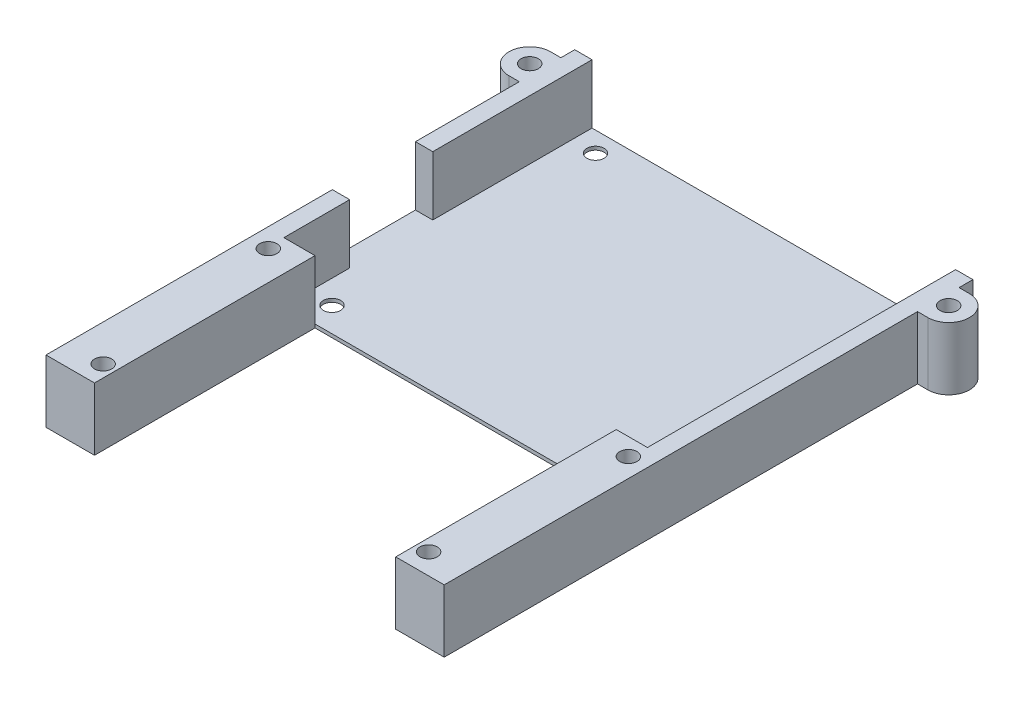
SolidWorks part; units mm, degrees
ref_plane "Front Plane" through (0, 0, 0) normal (0, 0, 1) x (1, 0, 0)
ref_plane "Top Plane" through (0, 0, 0) normal (0, 1, 0) x (1, 0, 0)
ref_plane "Right Plane" through (0, 0, 0) normal (1, 0, 0) x (0, 0, -1)
sketch "Sketch1" plane through (0, 0, 0) normal (0, 1, 0) x (1, 0, 0)
  line L0 (0, 0) -> (0, 76.35) construction
  line L1 (-28.75, 76.35) -> (28.75, 76.35)
  line L2 (28.75, 76.35) -> (28.75, 0)
  line L3 (28.75, 0) -> (21.75, 0)
  line L4 (21.75, 0) -> (21.75, 31.85)
  line L5 (21.75, 31.85) -> (-21.75, 31.85)
  line L6 (-21.75, 31.85) -> (-21.75, 0)
  line L7 (-21.75, 0) -> (-28.75, 0)
  line L8 (-28.75, 0) -> (-28.75, 76.35)
  line L9 (-26.25, 76.35) -> (-26.25, 31.85)
  line L14 (-26.25, 31.85) -> (-21.75, 31.85)
  line L15 (26.25, 76.35) -> (26.25, 31.85)
  line L16 (26.25, 31.85) -> (21.75, 31.85)
  line L17 (28.75, 74.35) -> (30.25, 74.35)
  line L18 (-28.75, 41.35) -> (-26.25, 41.35)
  line L19 (-28.75, 41.35) -> (-28.75, 53.35)
  line L20 (-28.75, 53.35) -> (-26.25, 53.35)
  line L21 (-26.25, 41.35) -> (-26.25, 53.35)
  line L22 (30.25, 68.35) -> (28.75, 68.35)
  line L23 (-30.25, 68.35) -> (-28.75, 68.35)
  line L24 (-28.75, 74.35) -> (-30.25, 74.35)
  arc A0 (30.25, 68.35) -> (30.25, 74.35) centre (30.25, 71.35) ccw
  arc A1 (-30.25, 68.35) -> (-30.25, 74.35) centre (-30.25, 71.35) cw
  point P10 (0, 76.35)
  point P16 (-27.5, 41.35)
  point P17 (-22.85, 73.45)
  point P18 (22.85, 73.45)
  point P23 (22.85, 35.4)
  point P24 (-22.85, 35.4)
  point P25 (23.5, 3)
  point P26 (26, 29.35)
  point P27 (-26, 29.35)
  point P28 (-23.5, 3)
  point P40 (30.25, 71.35)
  point P41 (-30.25, 71.35)
  dimension "D16" = 3
  dimension "D1" = 2.5
  dimension "D2" = 7
  dimension "D3" = 43.5
  dimension "D4" = 31.85
  dimension "D5" = 44.5
  dimension "D6" = 23
  dimension "D7" = 12
  dimension "D8" = 22.85
  dimension "D9" = 38.05
  dimension "D10" = 2.9
  dimension "D11" = 47
  dimension "D12" = 52
  dimension "D13" = 47
  dimension "D14" = 3
  dimension "D15" = 1.5
  dimension "D17" = 2
extrude "Boss-Extrude1" add sketch "Sketch1" along normal blind 0.5 contours L5 L0 L1 L9 L14 | L0 L5 L16 L15 L1 | L20 L8 L18 L9 region at (-13.125, 0, -54.1) region at (13.125, 0, -54.1) region at (-27.5, 0, -47.35)
extrude "Boss-Extrude2" add sketch "Sketch1<3>" along normal blind 9.05 contours L18 L8 L7 L6 L14 L9 | L8 L20 L9 L1 | L15 L16 L4 L3 L2 L1 | A1 L23 L8 L24 | L22 A0 L17 L2 region at (-27.5, 0, -64.85) region at (-30.7362, 0, -71.35) region at (25.999, 0, -28.6329) region at (-25.4666, 0, -17.9154) region at (30.7362, 0, -71.35)
sketch "Sketch1<3>" plane through (0, 0, 0) normal (0, 1, 0) x (1, 0, 0) same geometry as "Sketch1"
hole_wizard "Ø2.5 (2.5) Diameter Hole1" positions "Sketch4" profile "Sketch5" hole size "Ø2.5" standard "ANSI Metric"
sketch "Sketch4" plane through (0, 0, 0) normal (0, -1, 0) x (-1, 0, 0)
  point P0 (-22.85, 73.45)
  point P3 (22.85, 73.45)
  point P6 (26, 29.35)
  point P9 (22.85, 35.4)
  point P12 (-22.85, 35.4)
  point P15 (-26, 29.35)
  point P18 (-23.5, 3)
  point P21 (23.5, 3)
  point P24 (-30.25, 71.35)
  point P27 (30.25, 71.35)
sketch "Sketch5" plane through (22.85, 0, -73.45) normal (1, 0, 0) x (0, 0, -1)
  line L0 (0, 0) -> (0, 12.7511)
  line L1 (0, 12.7511) -> (1.25, 12)
  line L2 (1.25, 12) -> (1.25, 0)
  line L5 (1.25, 0) -> (0, 0)
  line L10 (0, 12.7511) -> (-1.25, 12) construction
  line L11 (0, -6.35) -> (0, 107.95) construction
  dimension "Hole Dia." = 2.5
  dimension "Hole Depth" = 12
  dimension "Drill Angle" = 118
